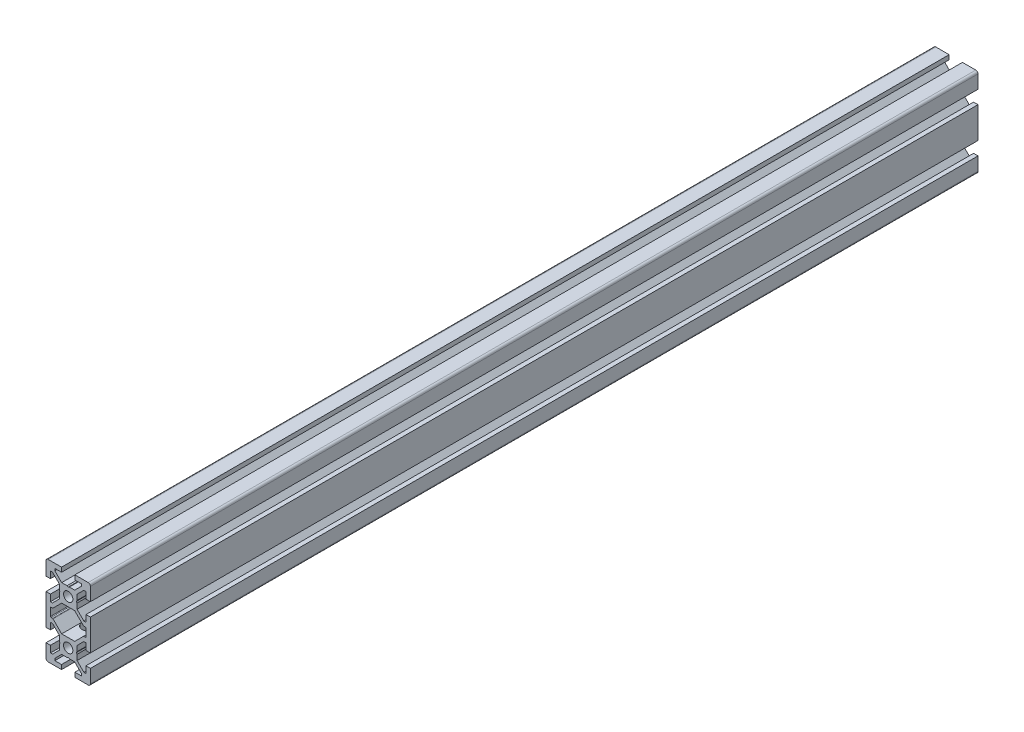
SolidWorks part; units mm, degrees
material "5052-H32"
ref_plane "Front Plane" through (0, 0, 0) normal (0, 0, 1) x (1, 0, 0)
ref_plane "Top Plane" through (0, 0, 0) normal (0, 1, 0) x (1, 0, 0)
ref_plane "Right Plane" through (0, 0, 0) normal (1, 0, 0) x (0, 0, -1)
sketch "Sketch1" plane through (0, 0, 0) normal (0, 0, 1) x (1, 0, 0)
  line L0 (-8, 4) -> (-8, 7)
  line L1 (-8, 7) -> (-10, 7)
  line L2 (-10, 7) -> (-10, -7)
  line L3 (-10, -7) -> (-8, -7)
  line L4 (-8, -7) -> (-8, -4)
  line L5 (-8, -4) -> (-7.0607, -4)
  line L6 (-7.0607, -4) -> (-4, -7.0607)
  line L7 (-4, -7.0607) -> (-4, -9.4804)
  line L8 (-4, -9.4804) -> (-3.7, -10)
  line L9 (-3.7, -10) -> (-4, -10.5196)
  line L10 (-4, -10.5196) -> (-4, -12.9393)
  line L11 (-4, -12.9393) -> (-7.0607, -16)
  line L12 (-7.0607, -16) -> (-8, -16)
  line L13 (-8, -16) -> (-8, -13)
  line L14 (-8, -13) -> (-10, -13)
  line L15 (-10, -13) -> (-10, -19)
  line L16 (-9, -20) -> (-3, -20)
  line L17 (-3, -20) -> (-3, -18)
  line L18 (-3, -18) -> (-6, -18)
  line L19 (-6, -18) -> (-6, -17.0607)
  line L20 (-6, -17.0607) -> (-2.9393, -14)
  line L21 (-2.9393, -14) -> (-0.5196, -14)
  line L22 (-0.5196, -14) -> (0, -13.7)
  line L23 (0, -13.7) -> (0.5196, -14)
  line L24 (0.5196, -14) -> (2.9393, -14)
  line L25 (2.9393, -14) -> (6, -17.0607)
  line L26 (6, -17.0607) -> (6, -18)
  line L27 (6, -18) -> (3, -18)
  line L28 (3, -18) -> (3, -20)
  line L29 (3, -20) -> (9, -20)
  line L30 (10, -19) -> (10, -13)
  line L31 (10, -13) -> (8, -13)
  line L32 (8, -13) -> (8, -16)
  line L33 (8, -16) -> (7.0607, -16)
  line L34 (7.0607, -16) -> (4, -12.9393)
  line L35 (4, -12.9393) -> (4, -10.5196)
  line L36 (4, -10.5196) -> (3.7, -10)
  line L37 (3.7, -10) -> (4, -9.4804)
  line L38 (4, -9.4804) -> (4, -7.0607)
  line L39 (4, -7.0607) -> (7.0607, -4)
  line L40 (7.0607, -4) -> (8, -4)
  line L41 (8, -4) -> (8, -7)
  line L42 (8, -7) -> (10, -7)
  line L43 (10, -7) -> (10, 7)
  line L44 (10, 7) -> (8, 7)
  line L45 (8, 7) -> (8, 4)
  line L46 (8, 4) -> (7.0607, 4)
  line L47 (7.0607, 4) -> (4, 7.0607)
  line L48 (4, 7.0607) -> (4, 9.4804)
  line L49 (4, 9.4804) -> (3.7, 10)
  line L50 (3.7, 10) -> (4, 10.5196)
  line L51 (4, 10.5196) -> (4, 12.9393)
  line L52 (4, 12.9393) -> (7.0607, 16)
  line L53 (7.0607, 16) -> (8, 16)
  line L54 (8, 16) -> (8, 13)
  line L55 (8, 13) -> (10, 13)
  line L56 (10, 13) -> (10, 19)
  line L57 (9, 20) -> (3, 20)
  line L58 (3, 20) -> (3, 18)
  line L59 (3, 18) -> (6, 18)
  line L60 (6, 18) -> (6, 17.0607)
  line L61 (6, 17.0607) -> (2.9393, 14)
  line L62 (2.9393, 14) -> (0.5196, 14)
  line L63 (0.5196, 14) -> (0, 13.7)
  line L64 (0, 13.7) -> (-0.5196, 14)
  line L65 (-0.5196, 14) -> (-2.9393, 14)
  line L66 (-2.9393, 14) -> (-6, 17.0607)
  line L67 (-6, 17.0607) -> (-6, 18)
  line L68 (-6, 18) -> (-3, 18)
  line L69 (-3, 18) -> (-3, 20)
  line L70 (-3, 20) -> (-9, 20)
  line L71 (-10, 19) -> (-10, 13)
  line L72 (-10, 13) -> (-8, 13)
  line L73 (-8, 13) -> (-8, 16)
  line L74 (-8, 16) -> (-7.0607, 16)
  line L75 (-7.0607, 16) -> (-4, 12.9393)
  line L76 (-4, 12.9393) -> (-4, 10.5196)
  line L77 (-4, 10.5196) -> (-3.7, 10)
  line L78 (-3.7, 10) -> (-4, 9.4804)
  line L79 (-4, 9.4804) -> (-4, 7.0607)
  line L80 (-4, 7.0607) -> (-7.0607, 4)
  line L81 (-7.0607, 4) -> (-8, 4)
  line L82 (-8, -1.7) -> (-8, 1.7)
  line L83 (-7.7, 2) -> (-7.0636, 2)
  line L84 (-6.8515, 2.0879) -> (-2.9393, 6)
  line L85 (-2.9393, 6) -> (2.9393, 6)
  line L86 (2.9393, 6) -> (6.8515, 2.0879)
  line L87 (7.0636, 2) -> (7.7, 2)
  line L88 (8, 1.7) -> (8, -1.7)
  line L89 (7.7, -2) -> (7.0636, -2)
  line L90 (6.8515, -2.0879) -> (2.9393, -6)
  line L91 (2.9393, -6) -> (-2.9393, -6)
  line L92 (-2.9393, -6) -> (-6.8515, -2.0879)
  line L93 (-7.0636, -2) -> (-7.7, -2)
  arc A0 (-10, -19) -> (-9, -20) centre (-9, -19) ccw
  arc A1 (9, -20) -> (10, -19) centre (9, -19) ccw
  arc A2 (10, 19) -> (9, 20) centre (9, 19) ccw
  arc A3 (-9, 20) -> (-10, 19) centre (-9, 19) ccw
  arc A4 (-7.7, -2) -> (-8, -1.7) centre (-7.7, -1.7) cw
  arc A5 (-8, 1.7) -> (-7.7, 2) centre (-7.7, 1.7) cw
  arc A6 (-7.0636, 2) -> (-6.8515, 2.0879) centre (-7.0636, 2.3) ccw
  arc A7 (6.8515, 2.0879) -> (7.0636, 2) centre (7.0636, 2.3) ccw
  arc A8 (7.7, 2) -> (8, 1.7) centre (7.7, 1.7) cw
  arc A9 (8, -1.7) -> (7.7, -2) centre (7.7, -1.7) cw
  arc A10 (7.0636, -2) -> (6.8515, -2.0879) centre (7.0636, -2.3) ccw
  arc A11 (-6.8515, -2.0879) -> (-7.0636, -2) centre (-7.0636, -2.3) ccw
  circle A12 centre (0, 10) radius 2.1
  circle A13 centre (0, -10) radius 2.1
extrude "Boss-Extrude1" add sketch "Sketch1" against normal blind 350
sketch "Sketch3" plane through (0, -14, 0) normal (0, -1, 0) x (1, 0, 0)
  circle A0 centre (0, -9) radius 2.75
  dimension "D1" = 5.5
extrude "Cut-Extrude1" cut sketch "Sketch3" against normal blind 10
sketch "Sketch4" plane through (0, 0, -350) normal (0, 0, -1) x (-1, 0, 0)
  line L0 (-2.9393, 6) -> (2.9393, 6) construction
  line L1 (2.9393, 6) -> (6.8515, 2.0879) construction
  line L2 (-6.8515, 2.0879) -> (-2.9393, 6) construction
  line L3 (-2.9393, 6) -> (2.9393, 6)
  line L4 (2.9393, 6) -> (6.8515, 2.0879)
  line L5 (-6.8515, 2.0879) -> (-2.9393, 6)
  line L6 (-7.7, 2) -> (-7.0636, 2) construction
  line L7 (-8, -1.7) -> (-8, 1.7) construction
  line L8 (-7.0636, -2) -> (-7.7, -2) construction
  line L9 (-2.9393, -6) -> (-6.8515, -2.0879) construction
  line L10 (2.9393, -6) -> (-2.9393, -6) construction
  line L11 (6.8515, -2.0879) -> (2.9393, -6) construction
  line L12 (7.7, -2) -> (7.0636, -2) construction
  line L13 (8, 1.7) -> (8, -1.7) construction
  line L14 (7.0636, 2) -> (7.7, 2) construction
  line L15 (-7.7, 2) -> (-7.0636, 2)
  line L16 (-8, -1.7) -> (-8, 1.7)
  line L17 (-7.0636, -2) -> (-7.7, -2)
  line L18 (-2.9393, -6) -> (-6.8515, -2.0879)
  line L19 (2.9393, -6) -> (-2.9393, -6)
  line L20 (6.8515, -2.0879) -> (2.9393, -6)
  line L21 (7.7, -2) -> (7.0636, -2)
  line L22 (8, 1.7) -> (8, -1.7)
  line L23 (7.0636, 2) -> (7.7, 2)
  line L82 (8, 4) -> (7.0607, 4)
  line L83 (7.0607, 4) -> (4, 7.0607)
  line L84 (4, 7.0607) -> (4, 9.4804)
  line L85 (4, 9.4804) -> (3.7, 10)
  line L86 (3.7, 10) -> (4, 10.5196)
  line L87 (4, 10.5196) -> (4, 12.9393)
  line L88 (4, 12.9393) -> (7.0607, 16)
  line L89 (7.0607, 16) -> (8, 16)
  line L90 (8, 16) -> (8, 13)
  line L91 (8, 13) -> (10, 13)
  line L92 (10, 13) -> (10, 19)
  line L93 (9, 20) -> (3, 20)
  line L94 (3, 20) -> (3, 18)
  line L95 (3, 18) -> (6, 18)
  line L96 (6, 18) -> (6, 17.0607)
  line L97 (6, 17.0607) -> (2.9393, 14)
  line L98 (2.9393, 14) -> (0.5196, 14)
  line L99 (0.5196, 14) -> (0, 13.7)
  line L100 (0, 13.7) -> (-0.5196, 14)
  line L101 (-0.5196, 14) -> (-2.9393, 14)
  line L102 (-2.9393, 14) -> (-6, 17.0607)
  line L103 (-6, 17.0607) -> (-6, 18)
  line L104 (-6, 18) -> (-3, 18)
  line L105 (-3, 18) -> (-3, 20)
  line L106 (-3, 20) -> (-9, 20)
  line L107 (-10, 19) -> (-10, 13)
  line L108 (-10, 13) -> (-8, 13)
  line L109 (-8, 13) -> (-8, 16)
  line L110 (-8, 16) -> (-7.0607, 16)
  line L111 (-7.0607, 16) -> (-4, 12.9393)
  line L112 (-4, 12.9393) -> (-4, 10.5196)
  line L113 (-4, 10.5196) -> (-3.7, 10)
  line L114 (-3.7, 10) -> (-4, 9.4804)
  line L115 (-4, 9.4804) -> (-4, 7.0607)
  line L116 (-4, 7.0607) -> (-7.0607, 4)
  line L117 (-7.0607, 4) -> (-8, 4)
  line L118 (-8, 4) -> (-8, 7)
  line L119 (-8, 7) -> (-10, 7)
  line L120 (-10, 7) -> (-10, -7)
  line L121 (-10, -7) -> (-8, -7)
  line L122 (-8, -7) -> (-8, -4)
  line L123 (-8, -4) -> (-7.0607, -4)
  line L124 (-7.0607, -4) -> (-4, -7.0607)
  line L125 (-4, -7.0607) -> (-4, -9.4804)
  line L126 (-4, -9.4804) -> (-3.7, -10)
  line L127 (-3.7, -10) -> (-4, -10.5196)
  line L128 (-4, -10.5196) -> (-4, -12.9393)
  line L129 (-4, -12.9393) -> (-7.0607, -16)
  line L130 (-7.0607, -16) -> (-8, -16)
  line L131 (-8, -16) -> (-8, -13)
  line L132 (-8, -13) -> (-10, -13)
  line L133 (-10, -13) -> (-10, -19)
  line L134 (-9, -20) -> (-3, -20)
  line L135 (-3, -20) -> (-3, -18)
  line L136 (-3, -18) -> (-6, -18)
  line L137 (-6, -18) -> (-6, -17.0607)
  line L138 (-6, -17.0607) -> (-2.9393, -14)
  line L139 (-2.9393, -14) -> (-0.5196, -14)
  line L140 (-0.5196, -14) -> (0, -13.7)
  line L141 (0, -13.7) -> (0.5196, -14)
  line L142 (0.5196, -14) -> (2.9393, -14)
  line L143 (2.9393, -14) -> (6, -17.0607)
  line L144 (6, -17.0607) -> (6, -18)
  line L145 (6, -18) -> (3, -18)
  line L146 (3, -18) -> (3, -20)
  line L147 (3, -20) -> (9, -20)
  line L148 (10, -19) -> (10, -13)
  line L149 (10, -13) -> (8, -13)
  line L150 (8, -13) -> (8, -16)
  line L151 (8, -16) -> (7.0607, -16)
  line L152 (7.0607, -16) -> (4, -12.9393)
  line L153 (4, -12.9393) -> (4, -10.5196)
  line L154 (4, -10.5196) -> (3.7, -10)
  line L155 (3.7, -10) -> (4, -9.4804)
  line L156 (4, -9.4804) -> (4, -7.0607)
  line L157 (4, -7.0607) -> (7.0607, -4)
  line L158 (7.0607, -4) -> (8, -4)
  line L159 (8, -4) -> (8, -7)
  line L160 (8, -7) -> (10, -7)
  line L161 (10, -7) -> (10, 7)
  line L162 (10, 7) -> (8, 7)
  line L163 (8, 7) -> (8, 4)
  line L164 (8, 4) -> (7.0607, 4)
  line L165 (7.0607, 4) -> (4, 7.0607)
  line L166 (4, 7.0607) -> (4, 9.4804)
  line L167 (4, 9.4804) -> (3.7, 10)
  line L168 (3.7, 10) -> (4, 10.5196)
  line L169 (4, 10.5196) -> (4, 12.9393)
  line L170 (4, 12.9393) -> (7.0607, 16)
  line L171 (7.0607, 16) -> (8, 16)
  line L172 (8, 16) -> (8, 13)
  line L173 (8, 13) -> (10, 13)
  line L174 (10, 13) -> (10, 19)
  line L175 (9, 20) -> (3, 20)
  line L176 (3, 20) -> (3, 18)
  line L177 (3, 18) -> (6, 18)
  line L178 (6, 18) -> (6, 17.0607)
  line L179 (6, 17.0607) -> (2.9393, 14)
  line L180 (2.9393, 14) -> (0.5196, 14)
  line L181 (0.5196, 14) -> (0, 13.7)
  line L182 (0, 13.7) -> (-0.5196, 14)
  line L183 (-0.5196, 14) -> (-2.9393, 14)
  line L184 (-2.9393, 14) -> (-6, 17.0607)
  line L185 (-6, 17.0607) -> (-6, 18)
  line L186 (-6, 18) -> (-3, 18)
  line L187 (-3, 18) -> (-3, 20)
  line L188 (-3, 20) -> (-9, 20)
  line L189 (-10, 19) -> (-10, 13)
  line L190 (-10, 13) -> (-8, 13)
  line L191 (-8, 13) -> (-8, 16)
  line L192 (-8, 16) -> (-7.0607, 16)
  line L193 (-7.0607, 16) -> (-4, 12.9393)
  line L194 (-4, 12.9393) -> (-4, 10.5196)
  line L195 (-4, 10.5196) -> (-3.7, 10)
  line L196 (-3.7, 10) -> (-4, 9.4804)
  line L197 (-4, 9.4804) -> (-4, 7.0607)
  line L198 (-4, 7.0607) -> (-7.0607, 4)
  line L199 (-7.0607, 4) -> (-8, 4)
  line L200 (-8, 4) -> (-8, 7)
  line L201 (-8, 7) -> (-10, 7)
  line L202 (-10, 7) -> (-10, -7)
  line L203 (-10, -7) -> (-8, -7)
  line L204 (-8, -7) -> (-8, -4)
  line L205 (-8, -4) -> (-7.0607, -4)
  line L206 (-7.0607, -4) -> (-4, -7.0607)
  line L207 (-4, -7.0607) -> (-4, -9.4804)
  line L208 (-4, -9.4804) -> (-3.7, -10)
  line L209 (-3.7, -10) -> (-4, -10.5196)
  line L210 (-4, -10.5196) -> (-4, -12.9393)
  line L211 (-4, -12.9393) -> (-7.0607, -16)
  line L212 (-7.0607, -16) -> (-8, -16)
  line L213 (-8, -16) -> (-8, -13)
  line L214 (-8, -13) -> (-10, -13)
  line L215 (-10, -13) -> (-10, -19)
  line L216 (-9, -20) -> (-3, -20)
  line L217 (-3, -20) -> (-3, -18)
  line L218 (-3, -18) -> (-6, -18)
  line L219 (-6, -18) -> (-6, -17.0607)
  line L220 (-6, -17.0607) -> (-2.9393, -14)
  line L221 (-2.9393, -14) -> (-0.5196, -14)
  line L222 (-0.5196, -14) -> (0, -13.7)
  line L223 (0, -13.7) -> (0.5196, -14)
  line L224 (0.5196, -14) -> (2.9393, -14)
  line L225 (2.9393, -14) -> (6, -17.0607)
  line L226 (6, -17.0607) -> (6, -18)
  line L227 (6, -18) -> (3, -18)
  line L228 (3, -18) -> (3, -20)
  line L229 (3, -20) -> (9, -20)
  line L230 (10, -19) -> (10, -13)
  line L231 (10, -13) -> (8, -13)
  line L232 (8, -13) -> (8, -16)
  line L233 (8, -16) -> (7.0607, -16)
  line L234 (7.0607, -16) -> (4, -12.9393)
  line L235 (4, -12.9393) -> (4, -10.5196)
  line L236 (4, -10.5196) -> (3.7, -10)
  line L237 (3.7, -10) -> (4, -9.4804)
  line L238 (4, -9.4804) -> (4, -7.0607)
  line L239 (4, -7.0607) -> (7.0607, -4)
  line L240 (7.0607, -4) -> (8, -4)
  line L241 (8, -4) -> (8, -7)
  line L242 (8, -7) -> (10, -7)
  line L243 (10, -7) -> (10, 7)
  line L244 (10, 7) -> (8, 7)
  line L245 (8, 7) -> (8, 4)
  circle A0 centre (0, 10) radius 2.1 construction
  circle A1 centre (0, -10) radius 2.1 construction
  circle A2 centre (0, 10) radius 2.1
  circle A3 centre (0, -10) radius 2.1
  arc A4 (10, 19) -> (9, 20) centre (9, 19) ccw
  arc A5 (-9, 20) -> (-10, 19) centre (-9, 19) ccw
  arc A6 (-10, -19) -> (-9, -20) centre (-9, -19) ccw
  arc A7 (9, -20) -> (10, -19) centre (9, -19) ccw
  arc A8 (10, 19) -> (9, 20) centre (9, 19) ccw
  arc A9 (-9, 20) -> (-10, 19) centre (-9, 19) ccw
  arc A10 (-10, -19) -> (-9, -20) centre (-9, -19) ccw
  arc A11 (9, -20) -> (10, -19) centre (9, -19) ccw
  arc A12 (-7.0636, 2) -> (-6.8515, 2.0879) centre (-7.0636, 2.3) ccw construction
  arc A13 (-7.7, 2) -> (-8, 1.7) centre (-7.7, 1.7) ccw construction
  arc A14 (-8, -1.7) -> (-7.7, -2) centre (-7.7, -1.7) ccw construction
  arc A15 (-6.8515, -2.0879) -> (-7.0636, -2) centre (-7.0636, -2.3) ccw construction
  arc A16 (7.0636, -2) -> (6.8515, -2.0879) centre (7.0636, -2.3) ccw construction
  arc A17 (7.7, -2) -> (8, -1.7) centre (7.7, -1.7) ccw construction
  arc A18 (8, 1.7) -> (7.7, 2) centre (7.7, 1.7) ccw construction
  arc A19 (6.8515, 2.0879) -> (7.0636, 2) centre (7.0636, 2.3) ccw construction
  arc A20 (-7.0636, 2) -> (-6.8515, 2.0879) centre (-7.0636, 2.3) ccw
  arc A21 (-7.7, 2) -> (-8, 1.7) centre (-7.7, 1.7) ccw
  arc A22 (-8, -1.7) -> (-7.7, -2) centre (-7.7, -1.7) ccw
  arc A23 (-6.8515, -2.0879) -> (-7.0636, -2) centre (-7.0636, -2.3) ccw
  arc A24 (7.0636, -2) -> (6.8515, -2.0879) centre (7.0636, -2.3) ccw
  arc A25 (7.7, -2) -> (8, -1.7) centre (7.7, -1.7) ccw
  arc A26 (8, 1.7) -> (7.7, 2) centre (7.7, 1.7) ccw
  arc A27 (6.8515, 2.0879) -> (7.0636, 2) centre (7.0636, 2.3) ccw
  dimension "D1" = 0
extrude "Boss-Extrude2" add sketch "Sketch4" along normal blind 50
